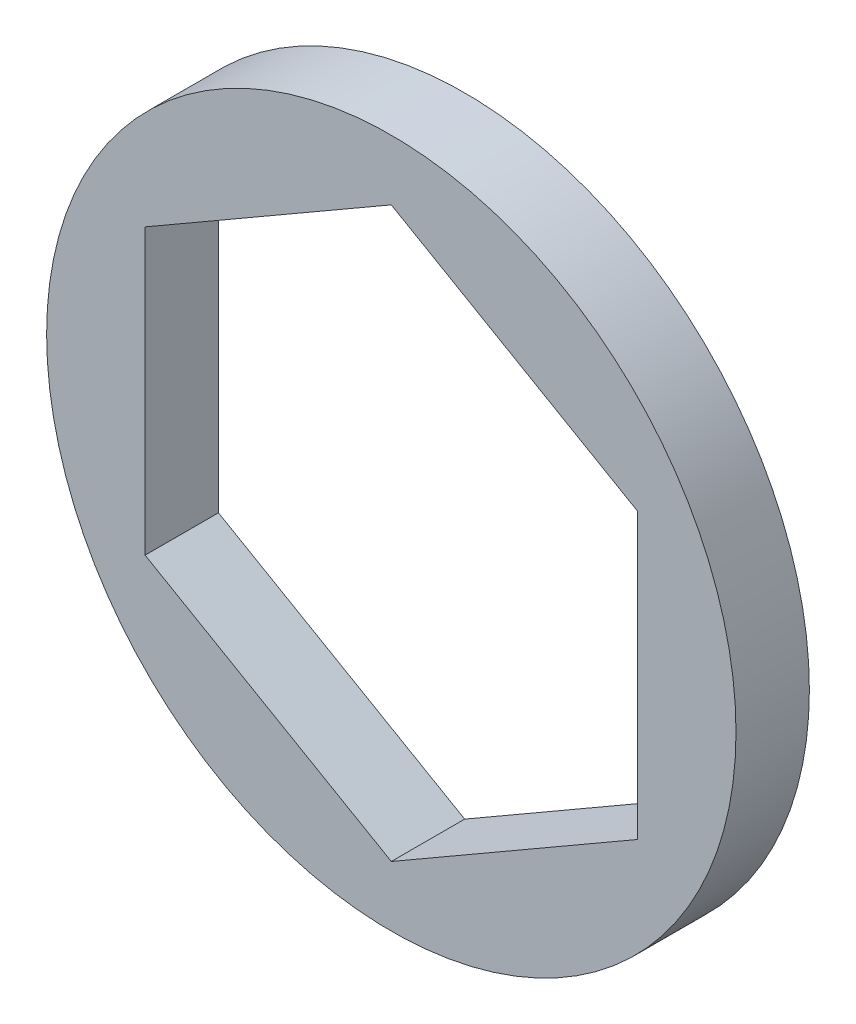
SolidWorks part; units mm, degrees
material "PET"
ref_plane "Front Plane" through (0, 0, 0) normal (0, 0, 1) x (1, 0, 0)
ref_plane "Top Plane" through (0, 0, 0) normal (0, 1, 0) x (1, 0, 0)
ref_plane "Right Plane" through (0, 0, 0) normal (1, 0, 0) x (0, 0, -1)
sketch "Sketch1" plane through (0, 0, 0) normal (0, 0, 1) x (1, 0, 0)
  line L1 (0, 7.3323) -> (-6.35, 3.6662)
  line L2 (-6.35, 3.6662) -> (-6.35, -3.6662)
  line L3 (-6.35, -3.6662) -> (0, -7.3323)
  line L4 (0, -7.3323) -> (6.35, -3.6662)
  line L5 (6.35, -3.6662) -> (6.35, 3.6662)
  line L6 (6.35, 3.6662) -> (0, 7.3323)
  circle A0 centre (0, 0) radius 8.89
  circle A1 centre (0, 0) radius 6.35 construction
  point P3 (0, 0)
  point P11 (0, 0)
  point P12 (0, 0)
  dimension "D1" = 17.78
  dimension "D2" = 12.7
extrude "Boss-Extrude1" add sketch "Sketch1" along normal mid plane 1.8923
